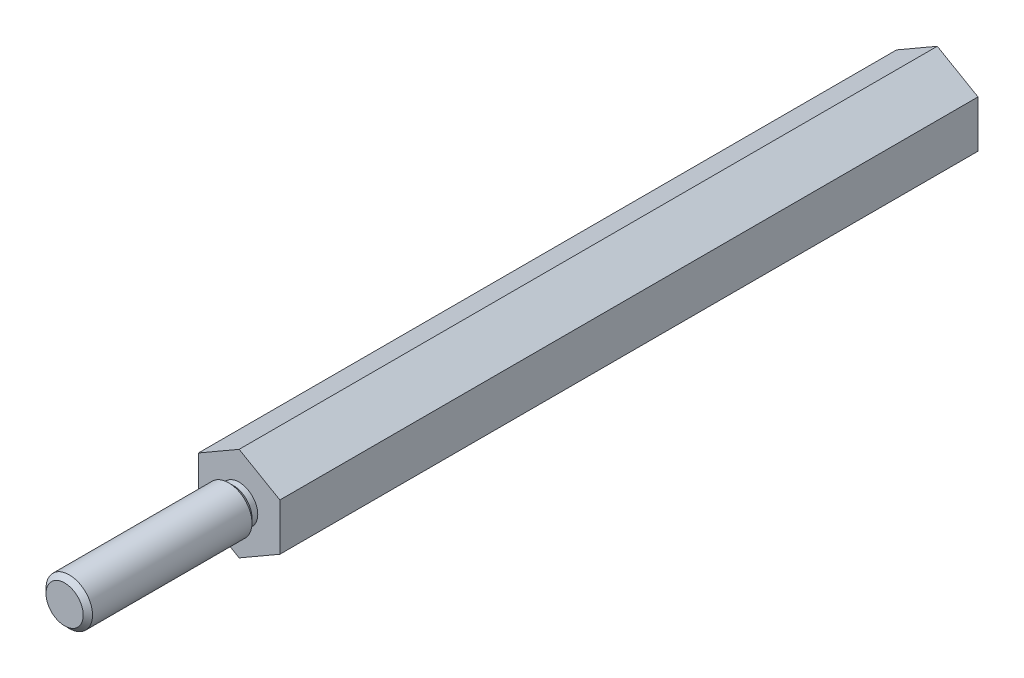
SolidWorks part; units mm, degrees
ref_plane "Спереди" through (0, 0, 0) normal (0, 0, 1) x (1, 0, 0)
ref_plane "Сверху" through (0, 0, 0) normal (0, 1, 0) x (1, 0, 0)
ref_plane "Справа" through (0, 0, 0) normal (1, 0, 0) x (0, 0, -1)
sketch "Эскиз1" plane through (0, 0, 0) normal (0, 0, 1) x (1, 0, 0)
  line L1 (0, 4.0415) -> (-3.5, 2.0207)
  line L2 (-3.5, 2.0207) -> (-3.5, -2.0207)
  line L3 (-3.5, -2.0207) -> (0, -4.0415)
  line L4 (0, -4.0415) -> (3.5, -2.0207)
  line L5 (3.5, -2.0207) -> (3.5, 2.0207)
  line L6 (3.5, 2.0207) -> (0, 4.0415)
  circle A0 centre (0, 0) radius 3.5 construction
  dimension "D1" = 7
extrude "Вытянуть1" add sketch "Эскиз1" along normal blind 60
sketch "Эскиз2" plane through (0, 0, 60) normal (0, 0, 1) x (1, 0, 0)
  circle A0 centre (0, 0) radius 2
  dimension "D1" = 4
extrude "Вытянуть2" add sketch "Эскиз2" along normal blind 15
sketch "Эскиз3" plane through (0, 0, 60) normal (0, 0, 1) x (1, 0, 0)
  circle A0 centre (0, 0) radius 1.6
  circle A1 centre (0, 0) radius 2 construction
  circle A2 centre (0, 0) radius 2
  dimension "D1" = 3.2
extrude "Вырез-Вытянуть3" cut sketch "Эскиз3" along normal blind 0.5
chamfer "Фаска1" distance 0.4 angle 45 2 edges at (2, 0, 60.5) (2, 0, 75)
hole_wizard "Отверстие с зазором M31" positions "Трехмерный эскиз2" profile "Эскиз5" hole size "M3" standard "Ansi Метрический"
sketch3d "Трехмерный эскиз2"
  point P0 (0, 0, 0)
  point P2 (0, 0, 0)
  point P3 (0, 0, 0)
sketch "Эскиз5" plane through (0, 0, 0) normal (1, 0, 0) x (0, 1, 0)
  line L0 (0, 0) -> (0, 8.6609)
  line L1 (0, 8.6609) -> (1.1, 8)
  line L2 (1.1, 8) -> (1.1, 0.4)
  line L3 (1.1, 0.4) -> (1.5, 0)
  line L5 (1.5, 0) -> (0, 0)
  line L6 (-1.1, 0.4) -> (-1.5, 0) construction
  line L10 (0, 8.6609) -> (-1.1, 8) construction
  line L11 (0, -6.35) -> (0, 107.95) construction
  dimension "Диаметр отверстия" = 2.2
  dimension "Глубина отверстия" = 8
  dimension "Диаметр передней зенковки" = 3
  dimension "Угол передней зенковки" = 90
  dimension "Угол заточки сверла" = 118
